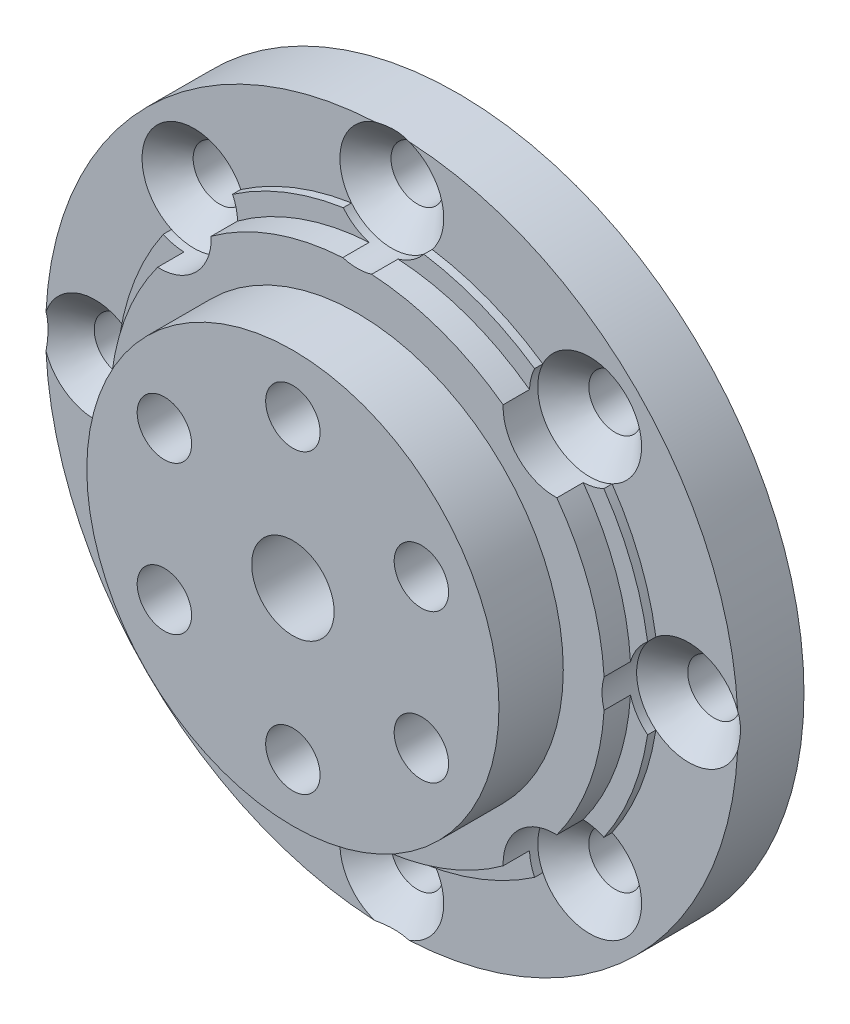
SolidWorks part; units mm, degrees
note: The reader was unsure of these and kept them because the rebuilt part matched: shared geometry of "ｽｹｯﾁ1<3>", "ｽｹｯﾁ1<4>", "ｽｹｯﾁ1<6>".
material "3.1325 (EN-AW 2017A)"
ref_plane "正面" through (0, 0, 0) normal (0, 0, 1) x (1, 0, 0)
ref_plane "平面" through (0, 0, 0) normal (0, 1, 0) x (1, 0, 0)
ref_plane "右側面" through (0, 0, 0) normal (1, 0, 0) x (0, 0, -1)
sketch "ｽｹｯﾁ1" plane through (0, 0, 0) normal (0, 0, 1) x (1, 0, 0)
  circle A0 centre (0, 0) radius 21
  circle A1 centre (0, 0) radius 15
  circle A2 centre (0, 0) radius 12.5
  circle A4 centre (0, 0) radius 18 construction
  circle A5 centre (0, 0) radius 9 construction
  circle A6 centre (0, 0) radius 16.2
  point P5 (12, 12)
  point P6 (0, 18)
  point P9 (0, 9)
  point P13 (18, 0)
  point P14 (0, -18)
  point P15 (-18, 0)
  point P17 (12, -12)
  point P18 (-12, -12)
  point P19 (-12, 12)
  point P20 (0, 0)
  point P21 (0, 0)
  point P25 (0, 0)
  point P67 (0, 0)
  dimension "D1" = 42
  dimension "D2" = 30
  dimension "D3" = 25
  dimension "D4" = 36
  dimension "D5" = 18
  dimension "D9" = 32.4
  dimension "D6" = 12
  dimension "D8" = 12
  dimension "D7" = 4
  dimension "D10" = 4
extrude "ﾎﾞｽ - 押し出し1" add sketch "ｽｹｯﾁ1" along normal blind 6.1 contours A1
extrude "ﾎﾞｽ - 押し出し2" add sketch "ｽｹｯﾁ1<3>" along normal blind 10 contours A2
sketch "ｽｹｯﾁ1<3>" plane through (0, 0, 0) normal (0, 0, 1) x (1, 0, 0) same geometry as "ｽｹｯﾁ1"
extrude "ﾎﾞｽ - 押し出し3" add sketch "ｽｹｯﾁ1<4>" along normal blind 4 contours A0
sketch "ｽｹｯﾁ1<4>" plane through (0, 0, 0) normal (0, 0, 1) x (1, 0, 0) same geometry as "ｽｹｯﾁ1"
extrude "ﾎﾞｽ - 押し出し4" add sketch "ｽｹｯﾁ1<6>" along normal blind 0.5 from surface at 4 contours A6 starting at face at (15, 0, 4)
sketch "ｽｹｯﾁ1<6>" plane through (0, 0, 0) normal (0, 0, 1) x (1, 0, 0) same geometry as "ｽｹｯﾁ1"
hole_wizard "M3 丸皿ねじ用皿穴1" positions "3Dｽｹｯﾁ2" profile "ｽｹｯﾁ2" countersink size "M3" standard "JIS"
sketch3d "3Dｽｹｯﾁ2"
  point P10 (0, 18, 4)
  point P20 (-18, 0, 4)
  point P22 (0, -18, 4)
  point P24 (18, 0, 4)
  point P79 (-12, -12, 0)
  point P81 (12, 12, 0)
  point P83 (12, -12, 0)
  point P85 (-12, 12, 0)
  point P90 (-12, 12, 0)
  point P92 (-12, -12, 0)
sketch "ｽｹｯﾁ2" plane through (0, 18, 4) normal (1, 0, 0) x (0, -1, 0)
  line L0 (0, 0) -> (0, 4)
  line L1 (0, 4) -> (1.6, 4)
  line L2 (1.6, 4) -> (1.6, 1.55)
  line L3 (1.6, 1.55) -> (3.15, 0)
  line L5 (3.15, 0) -> (0, 0)
  line L6 (-1.6, 1.55) -> (-3.15, 0) construction
  line L11 (0, -6.35) -> (0, 107.95) construction
  dimension "通し穴の直径" = 3.2
  dimension "通し穴の深さ" = 4
  dimension "表面の皿穴の直径" = 6.3
  dimension "表面の皿穴の角度" = 90
hole_wizard "M3 丸皿ねじ用皿穴2" positions "ｽｹｯﾁ7" profile "ｽｹｯﾁ8" countersink size "M3" standard "JIS"
sketch "ｽｹｯﾁ7" plane through (0, 0, 4) normal (0, 0, 1) x (1, 0, 0)
  point P0 (-12, 12)
  point P3 (12, 12)
  point P6 (-12, -12)
  point P9 (12, -12)
sketch "ｽｹｯﾁ8" plane through (-12, 12, 4) normal (1, 0, 0) x (0, -1, 0)
  line L0 (0, 0) -> (0, 4)
  line L1 (0, 4) -> (1.6, 4)
  line L2 (1.6, 4) -> (1.6, 1.55)
  line L3 (1.6, 1.55) -> (3.15, 0)
  line L5 (3.15, 0) -> (0, 0)
  line L6 (-1.6, 1.55) -> (-3.15, 0) construction
  line L11 (0, -6.35) -> (0, 107.95) construction
  dimension "通し穴の直径" = 3.2
  dimension "通し穴の深さ" = 4
  dimension "表面の皿穴の直径" = 6.3
  dimension "表面の皿穴の角度" = 90
hole_wizard "M5x0.8 ねじ穴1" positions "3Dｽｹｯﾁ4" profile "ｽｹｯﾁ6" tap size "M5x0.8" standard "JIS" end condition through all
sketch3d "3Dｽｹｯﾁ4"
  point P0 (0, 0, 10)
sketch "ｽｹｯﾁ6" plane through (0, 0, 10) normal (1, 0, 0) x (0, -1, 0)
  line L0 (0, 0) -> (0, 10)
  line L1 (0, 10) -> (2.5, 10)
  line L2 (2.5, 10) -> (2.5, 0)
  line L5 (2.5, 0) -> (0, 0)
  line L11 (0, -6.35) -> (0, 107.95) construction
  dimension "ねじ山の主要直径" = 5
  dimension "次ｻｰﾌｪｽまでのねじ下穴ﾄﾞﾘﾙの深さ" = 10
hole_wizard "M4x0.7 ねじ穴1" positions "3Dｽｹｯﾁ3" profile "ｽｹｯﾁ3" tap size "M4x0.7" standard "JIS"
sketch3d "3Dｽｹｯﾁ3"
  point P26 (0, 9, 10)
sketch "ｽｹｯﾁ3" plane through (0, 9, 10) normal (1, 0, 0) x (0, -1, 0)
  line L0 (0, 0) -> (0, 12.4914)
  line L1 (0, 12.4914) -> (1.65, 11.5)
  line L2 (1.65, 11.5) -> (1.65, 0)
  line L5 (1.65, 0) -> (0, 0)
  line L10 (0, 12.4914) -> (-1.65, 11.5) construction
  line L11 (0, -6.35) -> (0, 107.95) construction
  dimension "ねじ下穴ﾄﾞﾘﾙ直径" = 3.3
  dimension "ねじ下穴ﾄﾞﾘﾙの深さ" = 11.5
  dimension "ﾄﾞﾘﾙ角度" = 118
pattern_circular "円形ﾊﾟﾀｰﾝ1" count 6 over 360 about axis through (0, 0, 0) along (0, 0, 1) of "M4x0.7 ねじ穴1"
sketch "ｽｹｯﾁ5" plane through (0, 0, 0) normal (0, 0, 1) x (1, 0, 0)
  circle A0 centre (0, 18) radius 3.15
  circle A1 centre (12, -12) radius 3.15
  circle A2 centre (18, 0) radius 3.15
  circle A3 centre (0, -18) radius 3.15
  circle A4 centre (-18, 0) radius 3.15
  circle A5 centre (-12, -12) radius 3.15
  arc A6 (9.1596, 13.3619) -> (13.3619, 9.1596) centre (12, 12) ccw
  arc A7 (13.3619, 9.1596) -> (9.1596, 13.3619) centre (12, 12) ccw
  circle A8 centre (12, 12) radius 3.15
  circle A9 centre (0, 18) radius 3.15 construction
  circle A10 centre (-12, 12) radius 3.15
  point P22 (0, 0)
  point P27 (0, 0)
  dimension "D1" = 4
  dimension "D2" = 0
  dimension "D3" = 4
extrude "ｶｯﾄ - 押し出し3" cut sketch "ｽｹｯﾁ5" against normal up to surface (6 mm away) from offset 10
sketch "ｽｹｯﾁ9" plane through (0, 0, 10) normal (0, 0, 1) x (1, 0, 0)
  circle A0 centre (0, 0) radius 12.5 construction
  circle A1 centre (0, 0) radius 12.5
  arc A2 (-9.1596, -13.3619) -> (-13.3619, -9.1596) centre (-12, -12) ccw construction
  arc A3 (-16.0144, -2.4454) -> (-13.3619, -9.1596) centre (0, 0) ccw construction
  arc A4 (-16.0144, -2.4454) -> (-16.0144, 2.4454) centre (-18, 0) ccw construction
  arc A5 (-13.3619, 9.1596) -> (-16.0144, 2.4454) centre (0, 0) ccw construction
  arc A6 (-13.3619, 9.1596) -> (-9.1596, 13.3619) centre (-12, 12) ccw construction
  arc A7 (-2.4454, 16.0144) -> (-9.1596, 13.3619) centre (0, 0) ccw construction
  arc A8 (-2.4454, 16.0144) -> (2.4454, 16.0144) centre (0, 18) ccw construction
  arc A9 (9.1596, 13.3619) -> (2.4454, 16.0144) centre (0, 0) ccw construction
  arc A10 (9.1596, 13.3619) -> (13.3619, 9.1596) centre (12, 12) ccw construction
  arc A11 (16.0144, 2.4454) -> (13.3619, 9.1596) centre (0, 0) ccw construction
  arc A12 (16.0144, 2.4454) -> (16.0144, -2.4454) centre (18, 0) ccw construction
  arc A13 (13.3619, -9.1596) -> (16.0144, -2.4454) centre (0, 0) ccw construction
  arc A14 (13.3619, -9.1596) -> (9.1596, -13.3619) centre (12, -12) ccw construction
  arc A15 (2.4454, -16.0144) -> (9.1596, -13.3619) centre (0, 0) ccw construction
  arc A16 (2.4454, -16.0144) -> (-2.4454, -16.0144) centre (0, -18) ccw construction
  arc A17 (-9.1596, -13.3619) -> (-2.4454, -16.0144) centre (0, 0) ccw construction
  arc A18 (-12.1097, 8.8519) -> (-8.8519, 12.1097) centre (-12, 12) ccw
  arc A19 (-12.1097, 8.8519) -> (-14.9744, 0.8764) centre (0, 0) ccw
  arc A20 (-14.9744, -0.8764) -> (-14.9744, 0.8764) centre (-18, 0) ccw
  arc A21 (-14.9744, -0.8764) -> (-12.1097, -8.8519) centre (0, 0) ccw
  arc A22 (-8.8519, -12.1097) -> (-12.1097, -8.8519) centre (-12, -12) ccw
  arc A23 (-8.8519, -12.1097) -> (-0.8764, -14.9744) centre (0, 0) ccw
  arc A24 (0.8764, -14.9744) -> (-0.8764, -14.9744) centre (0, -18) ccw
  arc A25 (0.8764, -14.9744) -> (8.8519, -12.1097) centre (0, 0) ccw
  arc A26 (12.1097, -8.8519) -> (8.8519, -12.1097) centre (12, -12) ccw
  arc A27 (12.1097, -8.8519) -> (14.9744, -0.8764) centre (0, 0) ccw
  arc A28 (14.9744, 0.8764) -> (14.9744, -0.8764) centre (18, 0) ccw
  arc A29 (14.9744, 0.8764) -> (12.1097, 8.8519) centre (0, 0) ccw
  arc A30 (8.8519, 12.1097) -> (12.1097, 8.8519) centre (12, 12) ccw
  arc A31 (8.8519, 12.1097) -> (0.8764, 14.9744) centre (0, 0) ccw
  arc A32 (-0.8764, 14.9744) -> (0.8764, 14.9744) centre (0, 18) ccw
  arc A33 (-0.8764, 14.9744) -> (-8.8519, 12.1097) centre (0, 0) ccw
  arc A34 (-12.1097, 8.8519) -> (-8.8519, 12.1097) centre (-12, 12) ccw
  arc A35 (-12.1097, 8.8519) -> (-14.9744, 0.8764) centre (0, 0) ccw
  arc A36 (-14.9744, -0.8764) -> (-14.9744, 0.8764) centre (-18, 0) ccw
  arc A37 (-14.9744, -0.8764) -> (-12.1097, -8.8519) centre (0, 0) ccw
  arc A38 (-8.8519, -12.1097) -> (-12.1097, -8.8519) centre (-12, -12) ccw
  arc A39 (-8.8519, -12.1097) -> (-0.8764, -14.9744) centre (0, 0) ccw
  arc A40 (0.8764, -14.9744) -> (-0.8764, -14.9744) centre (0, -18) ccw
  arc A41 (0.8764, -14.9744) -> (8.8519, -12.1097) centre (0, 0) ccw
  arc A42 (12.1097, -8.8519) -> (8.8519, -12.1097) centre (12, -12) ccw
  arc A43 (12.1097, -8.8519) -> (14.9744, -0.8764) centre (0, 0) ccw
  arc A44 (14.9744, 0.8764) -> (14.9744, -0.8764) centre (18, 0) ccw
  arc A45 (14.9744, 0.8764) -> (12.1097, 8.8519) centre (0, 0) ccw
  arc A46 (8.8519, 12.1097) -> (12.1097, 8.8519) centre (12, 12) ccw
  arc A47 (8.8519, 12.1097) -> (0.8764, 14.9744) centre (0, 0) ccw
  arc A48 (-0.8764, 14.9744) -> (0.8764, 14.9744) centre (0, 18) ccw
  arc A49 (-0.8764, 14.9744) -> (-8.8519, 12.1097) centre (0, 0) ccw
  arc A50 (-9.1596, -13.3619) -> (-13.3619, -9.1596) centre (-12, -12) ccw
  arc A51 (-16.0144, -2.4454) -> (-13.3619, -9.1596) centre (0, 0) ccw
  arc A52 (-16.0144, -2.4454) -> (-16.0144, 2.4454) centre (-18, 0) ccw
  arc A53 (-13.3619, 9.1596) -> (-16.0144, 2.4454) centre (0, 0) ccw
  arc A54 (-13.3619, 9.1596) -> (-9.1596, 13.3619) centre (-12, 12) ccw
  arc A55 (-2.4454, 16.0144) -> (-9.1596, 13.3619) centre (0, 0) ccw
  arc A56 (-2.4454, 16.0144) -> (2.4454, 16.0144) centre (0, 18) ccw
  arc A57 (9.1596, 13.3619) -> (2.4454, 16.0144) centre (0, 0) ccw
  arc A58 (9.1596, 13.3619) -> (13.3619, 9.1596) centre (12, 12) ccw
  arc A59 (16.0144, 2.4454) -> (13.3619, 9.1596) centre (0, 0) ccw
  arc A60 (16.0144, 2.4454) -> (16.0144, -2.4454) centre (18, 0) ccw
  arc A61 (13.3619, -9.1596) -> (16.0144, -2.4454) centre (0, 0) ccw
  arc A62 (13.3619, -9.1596) -> (9.1596, -13.3619) centre (12, -12) ccw
  arc A63 (2.4454, -16.0144) -> (9.1596, -13.3619) centre (0, 0) ccw
  arc A64 (2.4454, -16.0144) -> (-2.4454, -16.0144) centre (0, -18) ccw
  arc A65 (-9.1596, -13.3619) -> (-2.4454, -16.0144) centre (0, 0) ccw
  dimension "D1" = 0
equation "\"フリッパ駆動ユニットプーリピン位置径\" = 18"
equation "\"D5@ｽｹｯﾁ1\"=\"フリッパ駆動ユニットプーリピン位置径\""
equation "\"フリッパ駆動ユニットプーリピン数\" = 6"
equation "\"D1@円形ﾊﾟﾀｰﾝ1\"=\"フリッパ駆動ユニットプーリピン数\""
